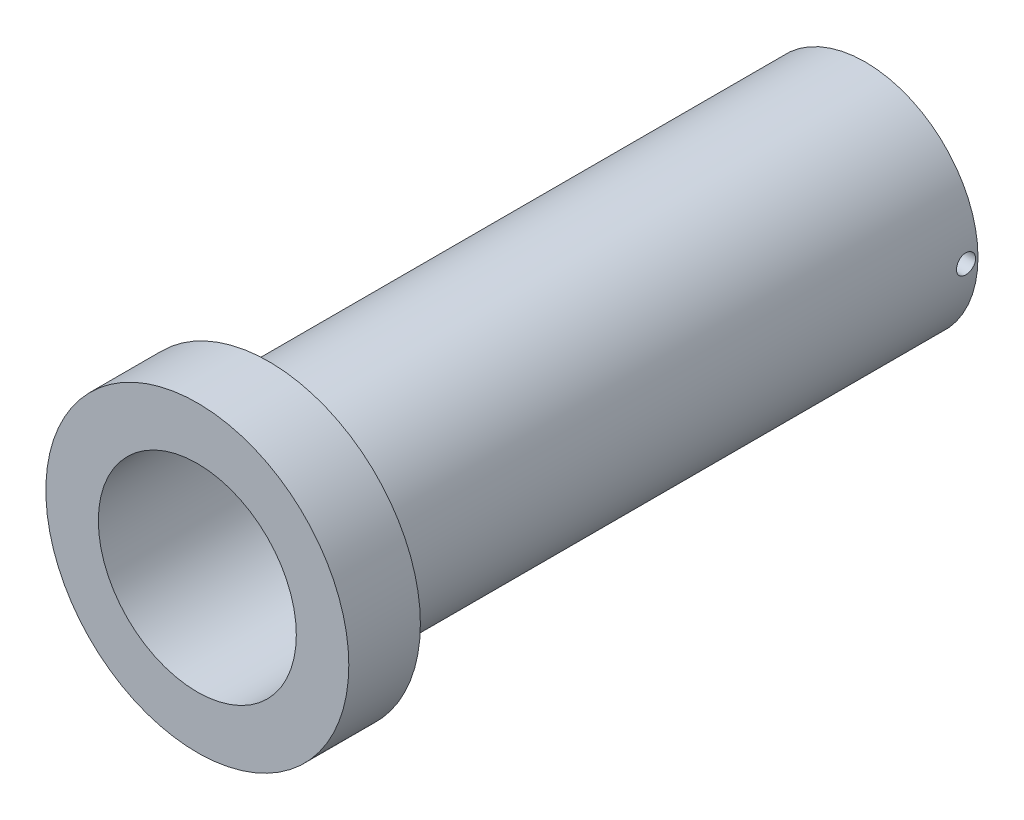
SolidWorks part; units mm, degrees
material "1060 Alloy"
ref_plane "Front Plane" through (0, 0, 0) normal (0, 0, 1) x (1, 0, 0)
ref_plane "Top Plane" through (0, 0, 0) normal (0, 1, 0) x (1, 0, 0)
ref_plane "Right Plane" through (0, 0, 0) normal (1, 0, 0) x (0, 0, -1)
sketch "Sketch1" plane through (0, 0, 0) normal (0, 0, 1) x (1, 0, 0)
  circle A0 centre (12.7336, -2.8837) radius 8.3
  arc A1 (11.2336, 5.2288) -> (4.958, -5.6409) centre (12.7336, -2.8837) ccw construction
  circle A2 centre (12.7336, -2.8837) radius 9.45
  arc A3 (5.0484, 3.1163) -> (5.0484, -8.8837) centre (12.7336, -2.8837) ccw construction
  dimension "D1" = 0.05
  dimension "D2" = 0.3
extrude "Boss-Extrude1" add sketch "Sketch1" along normal blind 50
sketch "Sketch2" plane through (0, 0, 50) normal (0, 0, 1) x (1, 0, 0)
  circle A0 centre (12.7336, -2.8837) radius 8.3
  circle A1 centre (12.7336, -2.8837) radius 8.3 construction
  circle A2 centre (12.7336, -2.8837) radius 12.7
  dimension "D1" = 25.4
extrude "Boss-Extrude2" add sketch "Sketch2" along normal blind 6
sketch3d "3DSketch1" plane through (0, 0, 0) normal (0, 0, 1) x (1, 0, 0)
sketch "Sketch5" plane through (22.1836, 0, 0) normal (1, 0, 0) x (0, 0, -1)
  line L0 (-15.5677, -2.8837) -> (63.1439, -2.8837) construction
  line L1 (0, -12.3337) -> (0, 6.5663) construction
  point P0 (-1, -2.8837)
  dimension "D1" = 1
hole_wizard "M2x0.4 Tapped Hole1" positions "3DSketch4" profile "Sketch7" tap size "M2x0.4" standard "Ansi Metric" end condition through all
sketch3d "3DSketch4"
  point P0 (22.1836, -2.8837, 1)
sketch "Sketch7" plane through (22.1836, -2.8837, 1) normal (0, 1, 0) x (0, 0, -1)
  line L0 (0, 0) -> (0, 22.15)
  line L1 (0, 22.15) -> (0.8, 22.15)
  line L2 (0.8, 22.15) -> (0.8, 0)
  line L5 (0.8, 0) -> (0, 0)
  line L11 (0, -6.35) -> (0, 107.95) construction
  dimension "Thru Tap Drill Dia." = 1.6
  dimension "Thru Tap Drill Depth" = 22.15
cosmetic thread "Hole Thread1" parameters "D2"=2
